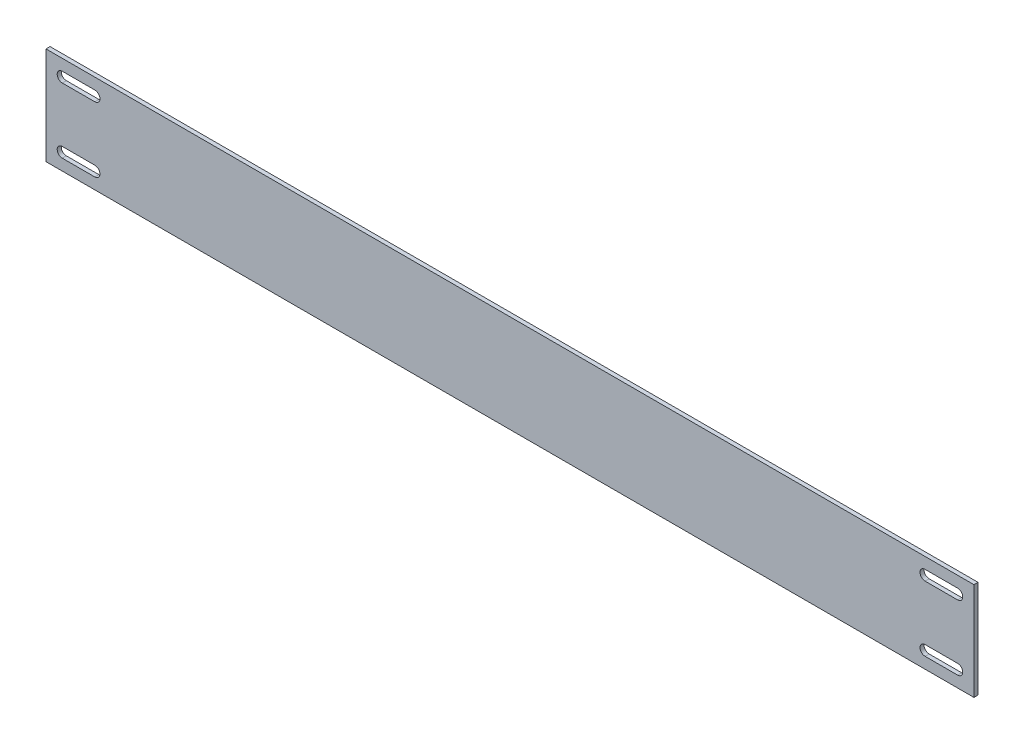
SolidWorks part; units mm, degrees
material "ABS"
ref_plane "Front Plane" through (0, 0, 0) normal (0, 0, 1) x (1, 0, 0)
ref_plane "Top Plane" through (0, 0, 0) normal (0, 1, 0) x (1, 0, 0)
ref_plane "Right Plane" through (0, 0, 0) normal (1, 0, 0) x (0, 0, -1)
sketch "Sketch1" plane through (0, 0, 0) normal (0, 1, 0) x (1, 0, 0)
  line L0 (0, 0) -> (361.95, 0)
  line L1 (361.95, 0) -> (361.95, 1.5875)
  line L2 (361.95, 1.5875) -> (336.55, 1.5875)
  line L5 (0, 0) -> (0, 1.5875)
  line L6 (0, 1.5875) -> (25.4, 1.5875)
  line L8 (25.4, 1.5875) -> (336.55, 1.5875)
  dimension "D1" = 361.95
  dimension "D2" = 25.4
  dimension "D3" = 1.5875
  dimension "D5" = 1.5875
  dimension "D6" = 25.4
extrude "Boss-Extrude1" add sketch "Sketch1" along normal blind 38.1
sketch "Sketch2" plane through (0, 0, -1.5875) normal (0, 0, -1) x (-1, 0, 0)
  line L0 (-180.975, 38.1) -> (-180.975, 0) construction
  line L3 (-25.4, 19.05) -> (0, 19.05) construction
  line L5 (0, 38.1) -> (0, 0) construction
  line L6 (-19.05, 31.75) -> (-6.35, 31.75) construction
  line L7 (-19.05, 33.7344) -> (-6.35, 33.7344)
  line L8 (-19.05, 29.7656) -> (-6.35, 29.7656)
  line L9 (-12.7, 19.05) -> (-12.7, 31.75) construction
  line L10 (-19.05, 6.35) -> (-6.35, 6.35) construction
  line L11 (-19.05, 4.3656) -> (-6.35, 4.3656)
  line L12 (-19.05, 8.3344) -> (-6.35, 8.3344)
  line L13 (-342.9, 6.35) -> (-355.6, 6.35) construction
  line L14 (-342.9, 4.3656) -> (-355.6, 4.3656)
  line L15 (-342.9, 8.3344) -> (-355.6, 8.3344)
  line L16 (-342.9, 31.75) -> (-355.6, 31.75) construction
  line L17 (-342.9, 33.7344) -> (-355.6, 33.7344)
  line L18 (-342.9, 29.7656) -> (-355.6, 29.7656)
  line L19 (0, 38.1) -> (0, 0) construction
  line L20 (-361.95, 38.1) -> (0, 38.1) construction
  line L21 (-361.95, 0) -> (0, 0) construction
  arc A0 (-19.05, 33.7344) -> (-19.05, 29.7656) centre (-19.05, 31.75) ccw
  arc A1 (-6.35, 29.7656) -> (-6.35, 33.7344) centre (-6.35, 31.75) ccw
  arc A2 (-19.05, 4.3656) -> (-19.05, 8.3344) centre (-19.05, 6.35) cw
  arc A3 (-6.35, 8.3344) -> (-6.35, 4.3656) centre (-6.35, 6.35) cw
  arc A4 (-342.9, 4.3656) -> (-342.9, 8.3344) centre (-342.9, 6.35) ccw
  arc A5 (-355.6, 8.3344) -> (-355.6, 4.3656) centre (-355.6, 6.35) ccw
  arc A6 (-342.9, 33.7344) -> (-342.9, 29.7656) centre (-342.9, 31.75) cw
  arc A7 (-355.6, 29.7656) -> (-355.6, 33.7344) centre (-355.6, 31.75) cw
  point P2 (-180.975, 38.1)
  point P14 (-12.7, 31.75)
  point P23 (-12.7, 6.35)
  point P30 (-349.25, 6.35)
  point P37 (-349.25, 31.75)
  dimension "D1" = 12.7
  dimension "D2" = 3.9688
  dimension "D3" = 12.7
  dimension "D4" = 12.7
extrude "Cut-Extrude2" cut sketch "Sketch2" against normal through all contours L8 A1 L7 A0 | A3 L12 A2 L11 | L15 A5 L14 A4 | A7 L18 A6 L17 | L18 A7 L17 A6 region at (12.7, 31.75, -1.5875) region at (12.7, 6.35, -1.5875) region at (349.25, 6.35, -1.5875) region at (349.25, 31.75, -1.5875)
